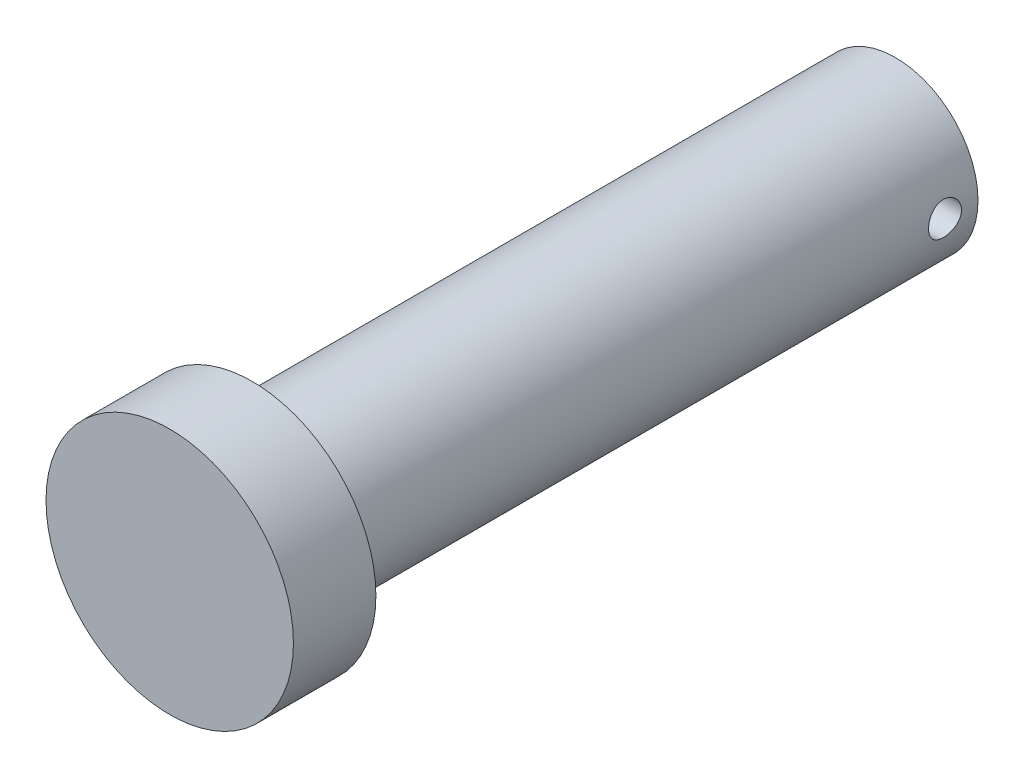
SolidWorks part; units mm, degrees
ref_plane "Front Plane" through (0, 0, 0) normal (0, 0, 1) x (1, 0, 0)
ref_plane "Top Plane" through (0, 0, 0) normal (0, 1, 0) x (1, 0, 0)
ref_plane "Right Plane" through (0, 0, 0) normal (1, 0, 0) x (0, 0, -1)
sketch "Sketch1" plane through (0, 0, 0) normal (0, 0, 1) x (1, 0, 0)
  circle A0 centre (0, 0) radius 5
  dimension "D1" = 10
extrude "Boss-Extrude1" add sketch "Sketch1" along normal blind 44
sketch "Sketch2" plane through (0, 0, 44) normal (0, 0, 1) x (1, 0, 0)
  circle A0 centre (0, 0) radius 7.5
  dimension "D1" = 15
extrude "Boss-Extrude2" add sketch "Sketch2" against normal blind 5
sketch "Sketch3" plane through (0, 0, 0) normal (1, 0, 0) x (0, 0, -1)
  line L0 (0, 0) -> (-2, 0) construction
  circle A0 centre (-2, 0) radius 1
  dimension "D2" = 2
  dimension "D1" = 2
extrude "Cut-Extrude1" cut sketch "Sketch3" against normal blind 5 and the other way blind 5
